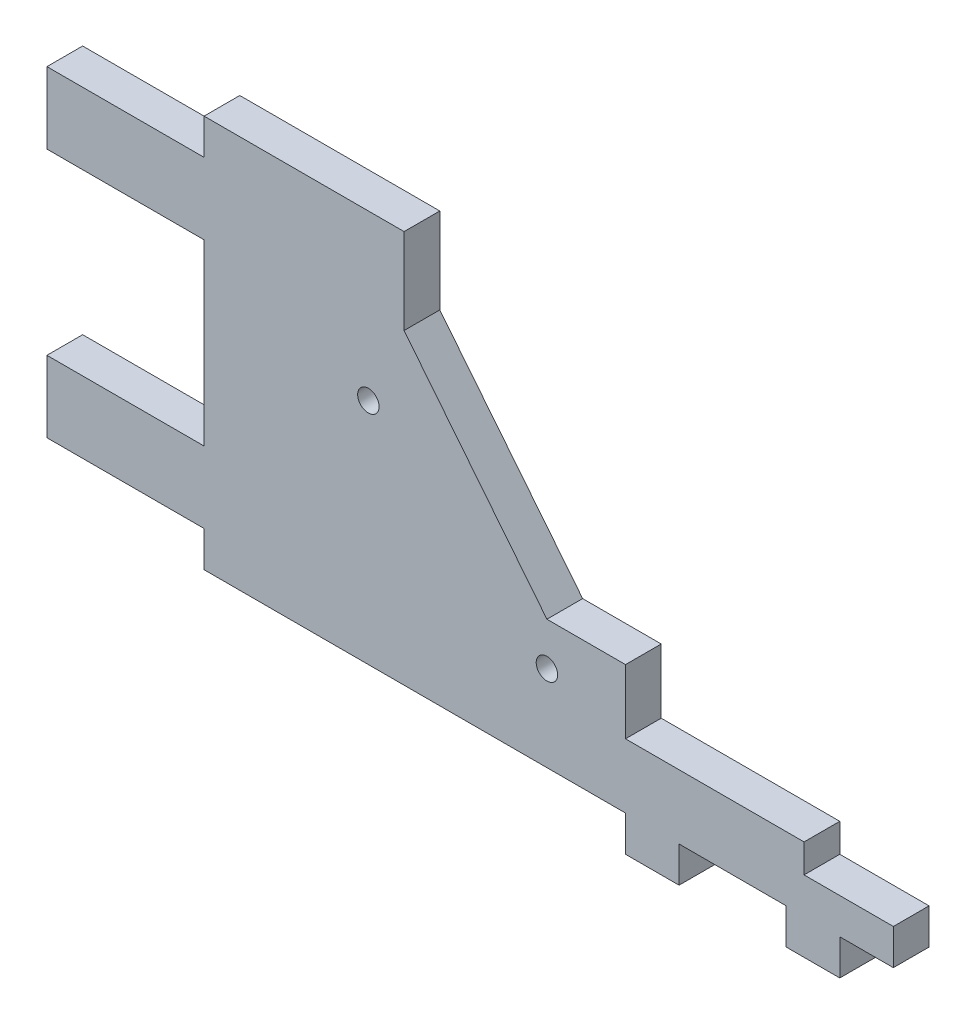
SolidWorks part; units mm, degrees
ref_plane "Plan de face" through (0, 0, 0) normal (0, 0, 1) x (1, 0, 0)
ref_plane "Plan de dessus" through (0, 0, 0) normal (0, 1, 0) x (1, 0, 0)
ref_plane "Plan de droite" through (0, 0, 0) normal (1, 0, 0) x (0, 0, -1)
sketch "Esquisse1" plane through (0, 0, 0) normal (0, 0, 1) x (1, 0, 0)
  line L0 (11, 43) -> (31, 18)
  line L1 (0, 0) -> (37, 0)
  line L2 (0, 0) -> (0, 55)
  line L3 (0, 55) -> (11, 55)
  line L4 (37, 0) -> (37, 18)
  line L6 (11, 55) -> (11, 43)
  line L7 (31, 18) -> (37, 18)
  circle A0 centre (6, 32) radius 1.5
  circle A1 centre (31, 12) radius 1.5
  point P1 (0, 0)
  dimension "D3" = 20
  dimension "D4" = 3
  dimension "D1" = 6
  dimension "D2" = 55
  dimension "D5" = 12
  dimension "D6" = 6
  dimension "D7" = 25
  dimension "D8" = 12
  dimension "D9" = 6
  dimension "D10" = 6
  dimension "D11" = 11
extrude "Boss.-Extru.1" add sketch "Esquisse1" along normal blind 5
sketch "Esquisse2" plane through (0, 0, 5) normal (0, 0, 1) x (1, 0, 0)
  line L0 (37, 18) -> (31, 18) construction
  line L1 (37, 0) -> (42, 0)
  line L2 (37, 0) -> (37, 18)
  line L3 (49.5, 0) -> (64.5, 0)
  line L4 (11, 55) -> (0, 55) construction
  line L5 (72, 0) -> (72, -5)
  line L6 (72, -5) -> (64.5, -5)
  line L7 (64.5, 0) -> (64.5, -5)
  line L8 (72, 0) -> (79.5, 0)
  line L9 (49.5, 0) -> (49.5, -5)
  line L10 (49.5, -5) -> (42, -5)
  line L11 (42, 0) -> (42, -5)
  line L12 (0, 0) -> (-17, 0)
  line L13 (0, 0) -> (0, 55)
  line L14 (0, 55) -> (-17, 55)
  line L15 (-17, 50) -> (-17, 55)
  line L16 (-17, 5) -> (-39, 5)
  line L17 (-17, 15) -> (-17, 40)
  line L18 (37, 18) -> (42, 18)
  line L19 (-17, 15) -> (-39, 15)
  line L20 (-17, 0) -> (-17, 5)
  line L21 (-39, 5) -> (-39, 15)
  line L22 (-17, 50) -> (-39, 50)
  line L23 (42, 18) -> (42, 9)
  line L24 (-17, 40) -> (-39, 40)
  line L25 (-39, 50) -> (-39, 40)
  line L26 (42, 9) -> (67, 9)
  line L27 (67, 9) -> (67, 5)
  line L28 (67, 5) -> (79.5, 5)
  line L29 (79.5, 5) -> (79.5, 0)
  circle A0 centre (31, 12) radius 1.5 construction
  dimension "D7" = 11
  dimension "D1" = 42.5
  dimension "D2" = 7.5
  dimension "D3" = 5
  dimension "D4" = 5
  dimension "D5" = 15
  dimension "D6" = 5
  dimension "D8" = 10
  dimension "D9" = 5
  dimension "D10" = 25
  dimension "D11" = 22
  dimension "D12" = 17
  dimension "D13" = 3
  dimension "D14" = 25
extrude "Boss.-Extru.2" add sketch "Esquisse2" against normal blind 5
